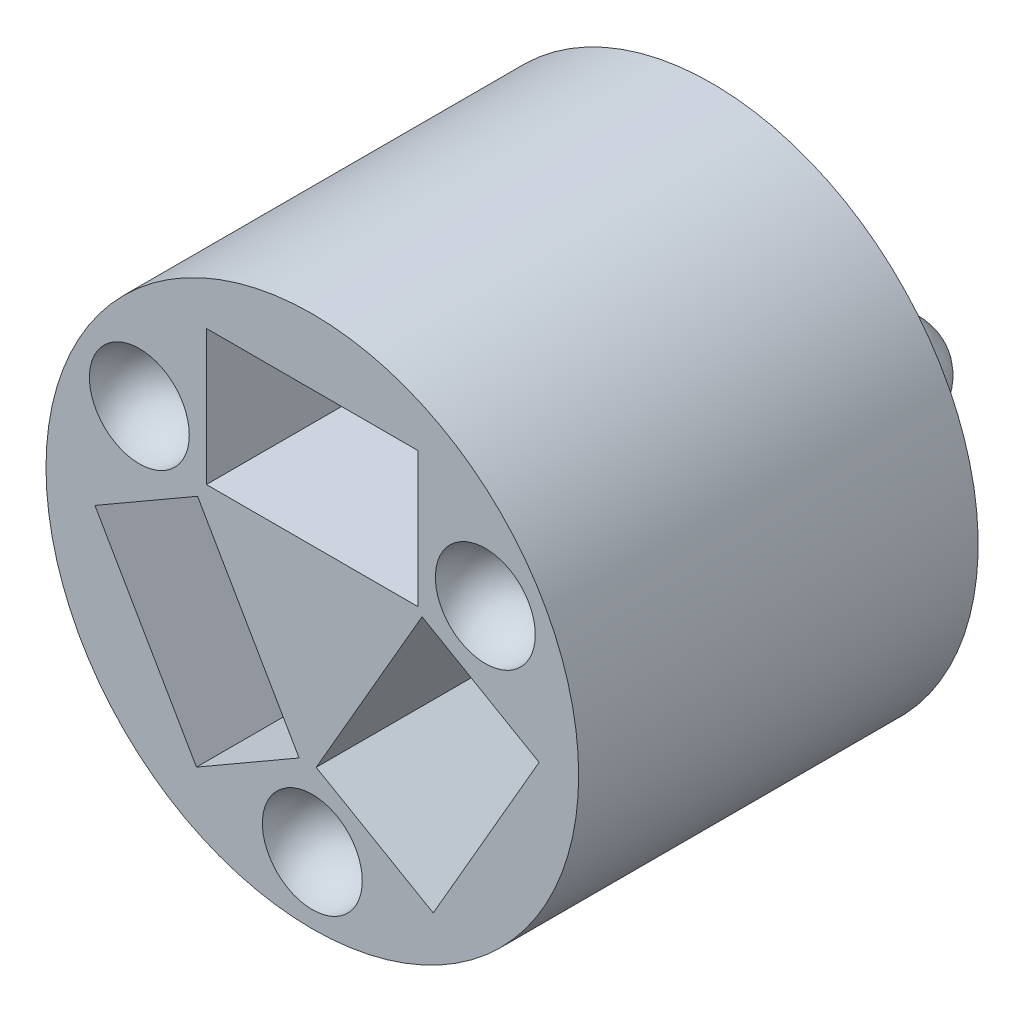
SolidWorks part; units mm, degrees
ref_plane "Front Plane" through (0, 0, 0) normal (0, 0, 1) x (1, 0, 0)
ref_plane "Top Plane" through (0, 0, 0) normal (0, 1, 0) x (1, 0, 0)
ref_plane "Right Plane" through (0, 0, 0) normal (1, 0, 0) x (0, 0, -1)
sketch "Sketch1" plane through (0, 0, 0) normal (0, 0, 1) x (1, 0, 0)
  line L0 (3.4061, -0.1305) -> (1.648, 0.8845)
  line L1 (-1.59, 0.985) -> (1.59, 0.985)
  line L2 (-1.59, 0.985) -> (-1.59, 3.015)
  line L3 (-1.59, 3.015) -> (1.59, 3.015)
  line L4 (1.59, 0.985) -> (1.59, 3.015)
  line L5 (-1.59, 0.985) -> (1.59, 3.015) construction
  line L6 (-1.59, 3.015) -> (1.59, 0.985) construction
  line L7 (3.4061, -0.1305) -> (1.8161, -2.8845)
  line L8 (1.648, 0.8845) -> (0.058, -1.8695)
  line L9 (1.8161, -2.8845) -> (0.058, -1.8695)
  line L10 (3.4061, -0.1305) -> (0.058, -1.8695) construction
  line L11 (1.648, 0.8845) -> (1.8161, -2.8845) construction
  line L12 (0, 0) -> (1.7321, -1) construction
  line L13 (-1.7403, -2.7657) -> (-0.1988, -1.8757)
  line L14 (-1.7403, -2.7657) -> (-3.2653, -0.1243)
  line L15 (-0.1988, -1.8757) -> (-1.7238, 0.7657)
  line L16 (-3.2653, -0.1243) -> (-1.7238, 0.7657)
  line L17 (-1.7403, -2.7657) -> (-1.7238, 0.7657) construction
  line L18 (-0.1988, -1.8757) -> (-3.2653, -0.1243) construction
  line L19 (-1.7321, -1) -> (0, 0) construction
  circle A0 centre (0, 0) radius 4
  circle A1 centre (0, 0) radius 2 construction
  point P3 (0, 2)
  point P8 (1.7321, -1)
  point P9 (-1.7321, -1)
  point P13 (0, 0)
  point P14 (-1.7321, -1)
  point P17 (0, 2)
  point P18 (1.7321, -1)
  dimension "D1" = 8
  dimension "D2" = 4
  dimension "D3" = 2.03
  dimension "D4" = 3.18
  dimension "D6" = 1.78
  dimension "D7" = 3.05
  dimension "D5" = 3
extrude "Boss-Extrude1" add sketch "Sketch1" along normal blind 5
sketch "Sketch4" plane through (0, 0, 0) normal (0, 0, -1) x (-1, 0, 0)
  circle A0 centre (0, 0) radius 4
  circle A1 centre (0, 0) radius 4 construction
  circle A2 centre (0, 2) radius 0.635
  circle A3 centre (1.7321, -1) radius 0.635
  circle A4 centre (-1.7321, -1) radius 0.635
  point P13 (0, 0)
  dimension "D2" = 1.27
  dimension "D1" = 2
  dimension "D3" = 3
extrude "Boss-Extrude3" add sketch "Sketch4" along normal blind 1
sketch "Sketch2" plane through (0, 0, -1) normal (0, 0, -1) x (-1, 0, 0)
  circle A0 centre (0, -3) radius 0.725
  circle A1 centre (-2.5981, 1.5) radius 0.725
  circle A2 centre (2.5981, 1.5) radius 0.725
  point P9 (0, 0)
  dimension "D1" = 1.45
  dimension "D2" = 3
  dimension "D3" = 3
extrude "Boss-Extrude2" add sketch "Sketch2" along normal blind 0.725
fillet "Fillet2" radius 0.725 3 edges at (-0.725, -3, -1.725) (-3.3231, 1.5, -1.725) (1.8731, 1.5, -1.725)
sketch "Sketch3" plane through (0, 0, 5) normal (0, 0, 1) x (1, 0, 0)
  circle A0 centre (0, -3) radius 0.75
  circle A1 centre (-2.5981, 1.5) radius 0.75
  circle A2 centre (2.5981, 1.5) radius 0.75
  point P9 (0, 0)
  dimension "D1" = 1.5
  dimension "D2" = 3
  dimension "D3" = 3
extrude "Cut-Extrude2" cut sketch "Sketch3" against normal blind 0.75
fillet "Fillet3" radius 0.75 3 edges at (0.75, -3, 4.25) (3.3481, 1.5, 4.25) (-1.8481, 1.5, 4.25)
